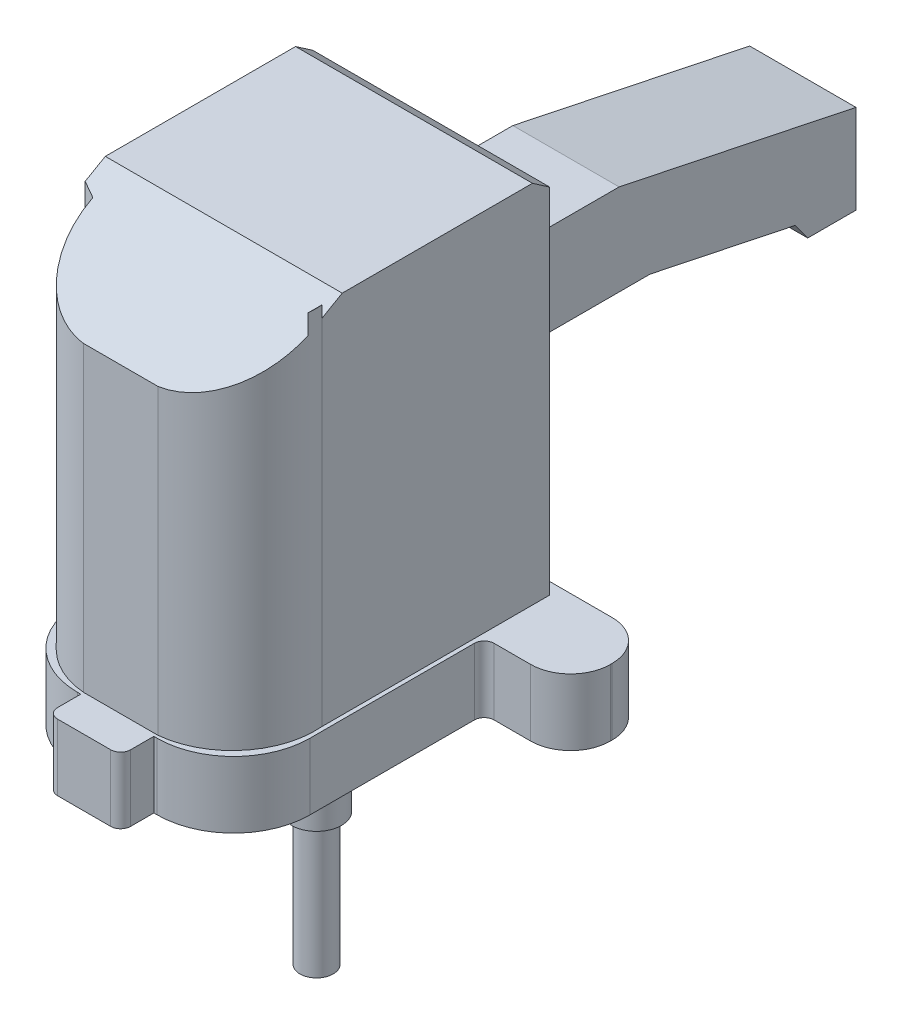
SolidWorks part; units mm, degrees
ref_plane "Спереди" through (0, 0, 0) normal (0, 0, 1) x (1, 0, 0)
ref_plane "Сверху" through (0, 0, 0) normal (0, 1, 0) x (1, 0, 0)
ref_plane "Справа" through (0, 0, 0) normal (1, 0, 0) x (0, 0, -1)
sketch "Эскиз1" plane through (0, 0, 0) normal (0, 1, 0) x (1, 0, 0)
  line L0 (35, 12.5) -> (35, -37)
  line L1 (-49, 40) -> (49, 40)
  line L3 (-8, -70) -> (8, -70)
  line L6 (-40, -32) -> (-40, 12.5)
  line L7 (-37, -35) -> (-35, -35)
  line L8 (38, 15.5) -> (49, 15.5)
  line L9 (61, 27.5) -> (61, 28)
  line L10 (-61, 28) -> (-61, 27.5)
  line L11 (-49, 15.5) -> (-43, 15.5)
  line L12 (-35, -35) -> (-35, -37)
  line L13 (-12, -60) -> (-11, -60)
  line L14 (-11, -60) -> (-11, -67)
  line L15 (11, -67) -> (11, -60)
  line L16 (11, -60) -> (12, -60)
  circle A0 centre (27.5, 27.5) radius 2
  circle A1 centre (-27.5, 27.5) radius 2
  circle A2 centre (-27.5, -27.5) radius 2
  circle A3 centre (27.5, -27.5) radius 2
  circle A4 centre (0, 0) radius 10
  arc A5 (49, 15.5) -> (61, 27.5) centre (49, 27.5) ccw
  arc A6 (-61, 27.5) -> (-49, 15.5) centre (-49, 27.5) ccw
  arc A7 (-49, 40) -> (-61, 28) centre (-49, 28) ccw
  arc A8 (61, 28) -> (49, 40) centre (49, 28) ccw
  arc A9 (-40, -32) -> (-37, -35) centre (-37, -32) ccw
  arc A10 (38, 15.5) -> (35, 12.5) centre (38, 12.5) ccw
  arc A11 (-40, 12.5) -> (-43, 15.5) centre (-43, 12.5) ccw
  arc A14 (-35, -37) -> (-12, -60) centre (-12, -37) ccw
  arc A15 (12, -60) -> (35, -37) centre (12, -37) ccw
  arc A16 (8, -70) -> (11, -67) centre (8, -67) ccw
  arc A17 (-8, -70) -> (-11, -67) centre (-8, -67) cw
  point P30 (-40, -35)
  dimension "D3" = 12
  dimension "D4" = 3
  dimension "D5" = 23
  dimension "D6" = 3
  dimension "D1" = 2
  dimension "D2" = 2
extrude "Бобышка-Вытянуть1" add sketch "Эскиз1" along normal blind 20
sketch "Эскиз2" plane through (0, 0, 0) normal (0, -1, 0) x (1, 0, 0)
  circle A0 centre (0, 0) radius 25
  circle A1 centre (0, 0) radius 12
extrude "Бобышка-Вытянуть2" add sketch "Эскиз2" along normal blind 2
sketch "Эскиз3" plane through (0, 20, 0) normal (0, 1, 0) x (1, 0, 0)
  line L0 (-37.5837, -32.1035) -> (-37.5837, 36.4574)
  line L1 (-37.5837, 36.4574) -> (-16, 36.4574)
  line L2 (33.7666, 36.4574) -> (33.7666, -32.1035)
  line L3 (-37.5837, -32.1035) -> (-33.3262, -34.0483)
  line L4 (-11, -59.1168) -> (11.3045, -59.1168)
  line L6 (16, 36.4574) -> (33.7666, 36.4574)
  line L7 (-16, 36.4574) -> (-16, 146.4574)
  line L8 (-16, 146.4574) -> (16, 146.4574)
  line L9 (16, 146.4574) -> (16, 36.4574)
  arc A0 (33.7666, -32.1035) -> (11.3045, -59.1168) centre (8.8578, -34.2369) cw
  arc A1 (-33.3262, -34.0483) -> (-11, -59.1168) centre (-9.2191, -35.0546) ccw
extrude "Бобышка-Вытянуть3" add sketch "Эскиз3" along normal blind 110
sketch "Эскиз4" plane through (33.7666, 0, 0) normal (1, 0, 0) x (0, 0, -1)
  line L0 (-59.1168, 111.0091) -> (-59.1168, 20)
  line L1 (-59.1168, 130) -> (-59.1168, 20) construction
  line L3 (36.4574, 20) -> (36.4574, 70.8265)
  line L4 (36.4574, 130) -> (36.4574, 20) construction
  line L5 (36.4574, 70.8265) -> (84.4124, 70.8265)
  line L6 (84.4124, 70.8265) -> (128.1932, 61.6738)
  line L7 (128.1932, 61.6738) -> (131.9337, 56.4999)
  line L8 (131.9337, 56.4999) -> (146.4574, 56.4999)
  line L9 (146.4574, 130) -> (146.4574, 20) construction
  line L10 (146.4574, 56.4999) -> (146.4574, 83.3278)
  line L11 (146.4574, 83.3278) -> (75.1219, 98.241)
  line L12 (75.1219, 98.241) -> (43.3924, 98.241)
  line L13 (43.3924, 98.241) -> (36.4574, 102.0797)
  line L14 (36.4574, 130) -> (36.4574, 20) construction
  line L15 (36.4574, 102.0797) -> (36.4574, 126.416)
  line L16 (36.4574, 126.416) -> (31.2624, 130)
  line L17 (-32.1035, 130) -> (36.4574, 130) construction
  line L18 (31.2624, 130) -> (-26.0369, 130)
  line L19 (-26.0369, 130) -> (-59.1168, 111.0091)
  line L21 (36.4574, 20) -> (40, 20)
  line L22 (40, 20) -> (40, 0)
  line L23 (40, 0) -> (25.5, 0)
  line L24 (25.5, 0) -> (25.5, -2.4657)
  line L25 (25.5, -2.4657) -> (-25.617, -2.4657)
  line L26 (-25.617, -2.4657) -> (-25.617, 0)
  line L27 (-37, 0) -> (12.5, 0) construction
  line L28 (-25.617, 0) -> (-70, 0)
  line L29 (-70, 20) -> (-70, 0) construction
  line L30 (-70, 0) -> (-67, 0) construction
  line L31 (-70, 0) -> (-70, 20)
  line L32 (-70, 20) -> (-59.1168, 20)
extrude "Вырез-Вытянуть5" cut sketch "Эскиз4" against normal through all flip side to cut
sketch "Эскиз5" plane through (0, 20, 0) normal (0, -1, 0) x (1, 0, 0)
  circle A0 centre (0, 0) radius 7.5
extrude "Бобышка-Вытянуть4" add sketch "Эскиз5" along normal blind 55
sketch "Эскиз6" plane through (0, -35, 0) normal (0, -1, 0) x (1, 0, 0)
  circle A0 centre (0, 0) radius 5
extrude "Бобышка-Вытянуть5" add sketch "Эскиз6" along normal blind 40
